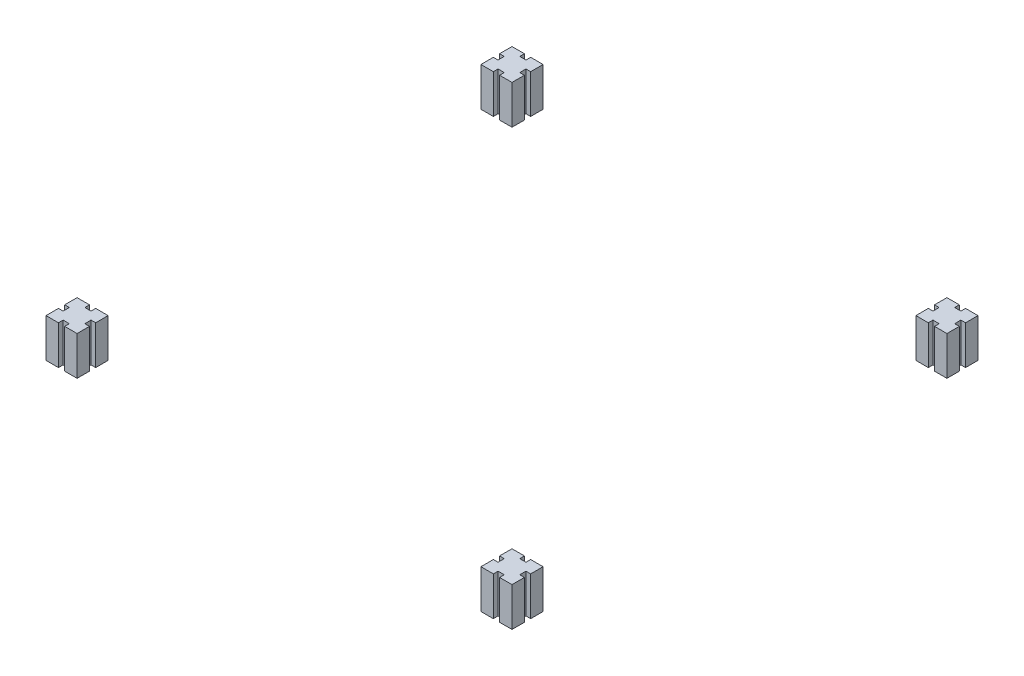
SolidWorks part; units mm, degrees
ref_plane "Front Plane" through (0, 0, 0) normal (0, 0, 1) x (1, 0, 0)
ref_plane "Top Plane" through (0, 0, 0) normal (0, 1, 0) x (1, 0, 0)
ref_plane "Right Plane" through (0, 0, 0) normal (1, 0, 0) x (0, 0, -1)
sketch "Sketch1" plane through (0, 0, 0) normal (0, 1, 0) x (1, 0, 0)
  line L0 (260, 300) -> (-260, 300) construction
  line L1 (-280, -280) -> (280, -280)
  line L2 (-280, -280) -> (-280, 280)
  line L3 (-280, 280) -> (280, 280)
  line L4 (280, -280) -> (280, 280)
  line L5 (-280, -280) -> (280, 280) construction
  line L6 (-280, 280) -> (280, -280) construction
  point P0 (0, 0)
  dimension "D1" = 20
  dimension "D2" = 45
sketch "Sketch2" plane through (0, 0, 0) normal (0, 1, 0) x (1, 0, 0)
  line L0 (0, -44) -> (0, 44) construction
  line L1 (-300, 300) -> (-260, 300)
  line L2 (-300, 300) -> (-300, 260)
  line L3 (-300, 260) -> (-260, 260)
  line L4 (-260, 300) -> (-260, 260)
  line L5 (-300, 300) -> (-260, 260) construction
  line L6 (-300, 260) -> (-260, 300) construction
  line L7 (300, 260) -> (260, 300) construction
  line L8 (300, 300) -> (260, 260) construction
  line L9 (260, 300) -> (260, 260)
  line L10 (300, 260) -> (260, 260)
  line L11 (300, 300) -> (300, 260)
  line L12 (300, 300) -> (260, 300)
  line L13 (-44, 0) -> (44, 0) construction
  line L14 (300, -300) -> (260, -260) construction
  line L15 (300, -260) -> (260, -300) construction
  line L16 (-300, -260) -> (-260, -300) construction
  line L17 (-300, -300) -> (-260, -260) construction
  line L18 (300, -300) -> (260, -300)
  line L19 (300, -300) -> (300, -260)
  line L20 (300, -260) -> (260, -260)
  line L21 (260, -300) -> (260, -260)
  line L22 (-260, -300) -> (-260, -260)
  line L23 (-300, -260) -> (-260, -260)
  line L24 (-300, -300) -> (-300, -260)
  line L25 (-300, -300) -> (-260, -300)
  point P0 (-280, 280)
  point P12 (280, 280)
  point P23 (280, -280)
  point P24 (-280, -280)
  dimension "D1" = 40
  dimension "D2" = 40
extrude "Boss-Extrude1" add sketch "Sketch2" along normal blind 25 and the other way blind 25
sketch "Sketch3" plane through (0, 0, 0) normal (0, 1, 0) x (1, 0, 0)
  line L0 (-280, 300) -> (-280, 260) construction
  line L1 (-260, 300) -> (-300, 300) construction
  line L2 (-300, 260) -> (-260, 260) construction
  line L3 (-300, 280) -> (-260, 280) construction
  line L4 (-300, 300) -> (-300, 260) construction
  line L5 (-260, 260) -> (-260, 300) construction
  line L6 (-254, 284) -> (-254, 276)
  line L7 (-284, 306) -> (-276, 306)
  line L8 (-284, 306) -> (-284, 294)
  line L9 (-284, 294) -> (-276, 294)
  line L10 (-276, 306) -> (-276, 294)
  line L11 (-284, 306) -> (-276, 294) construction
  line L12 (-284, 294) -> (-276, 306) construction
  line L13 (-254, 284) -> (-266, 284)
  line L14 (-266, 284) -> (-266, 276)
  line L15 (-254, 276) -> (-266, 276)
  line L16 (-254, 284) -> (-266, 276) construction
  line L17 (-266, 284) -> (-254, 276) construction
  line L18 (-276, 254) -> (-284, 254)
  line L19 (-276, 254) -> (-276, 266)
  line L20 (-276, 266) -> (-284, 266)
  line L21 (-284, 254) -> (-284, 266)
  line L22 (-276, 254) -> (-284, 266) construction
  line L23 (-276, 266) -> (-284, 254) construction
  line L24 (-306, 276) -> (-306, 284)
  line L25 (-306, 276) -> (-294, 276)
  line L26 (-294, 276) -> (-294, 284)
  line L27 (-306, 284) -> (-294, 284)
  line L28 (-306, 276) -> (-294, 284) construction
  line L29 (-294, 276) -> (-306, 284) construction
  line L30 (0, -55) -> (0, 55) construction
  line L31 (294, 276) -> (306, 284) construction
  line L32 (306, 276) -> (294, 284) construction
  line L33 (276, 266) -> (284, 254) construction
  line L34 (276, 254) -> (284, 266) construction
  line L35 (266, 284) -> (254, 276) construction
  line L36 (254, 284) -> (266, 276) construction
  line L37 (284, 294) -> (276, 306) construction
  line L38 (284, 306) -> (276, 294) construction
  line L39 (300, 280) -> (260, 280) construction
  line L40 (280, 300) -> (280, 260) construction
  line L41 (306, 284) -> (294, 284)
  line L42 (294, 276) -> (294, 284)
  line L43 (306, 276) -> (294, 276)
  line L44 (306, 276) -> (306, 284)
  line L45 (284, 254) -> (284, 266)
  line L46 (276, 266) -> (284, 266)
  line L47 (276, 254) -> (276, 266)
  line L48 (276, 254) -> (284, 254)
  line L49 (254, 276) -> (266, 276)
  line L50 (266, 284) -> (266, 276)
  line L51 (254, 284) -> (266, 284)
  line L52 (276, 306) -> (276, 294)
  line L53 (284, 294) -> (276, 294)
  line L54 (284, 306) -> (284, 294)
  line L55 (284, 306) -> (276, 306)
  line L56 (254, 284) -> (254, 276)
  line L57 (-55, 0) -> (55, 0) construction
  line L58 (280, -300) -> (280, -260) construction
  line L59 (300, -280) -> (260, -280) construction
  line L60 (284, -306) -> (276, -294) construction
  line L61 (284, -294) -> (276, -306) construction
  line L62 (254, -284) -> (266, -276) construction
  line L63 (266, -284) -> (254, -276) construction
  line L64 (276, -254) -> (284, -266) construction
  line L65 (276, -266) -> (284, -254) construction
  line L66 (306, -276) -> (294, -284) construction
  line L67 (294, -276) -> (306, -284) construction
  line L68 (-294, -276) -> (-306, -284) construction
  line L69 (-306, -276) -> (-294, -284) construction
  line L70 (-276, -266) -> (-284, -254) construction
  line L71 (-276, -254) -> (-284, -266) construction
  line L72 (-266, -284) -> (-254, -276) construction
  line L73 (-254, -284) -> (-266, -276) construction
  line L74 (-284, -294) -> (-276, -306) construction
  line L75 (-284, -306) -> (-276, -294) construction
  line L76 (-300, -280) -> (-260, -280) construction
  line L77 (-280, -300) -> (-280, -260) construction
  line L78 (254, -284) -> (254, -276)
  line L79 (284, -306) -> (276, -306)
  line L80 (284, -306) -> (284, -294)
  line L81 (284, -294) -> (276, -294)
  line L82 (276, -306) -> (276, -294)
  line L83 (254, -284) -> (266, -284)
  line L84 (266, -284) -> (266, -276)
  line L85 (254, -276) -> (266, -276)
  line L86 (276, -254) -> (284, -254)
  line L87 (276, -254) -> (276, -266)
  line L88 (276, -266) -> (284, -266)
  line L89 (284, -254) -> (284, -266)
  line L90 (306, -276) -> (306, -284)
  line L91 (306, -276) -> (294, -276)
  line L92 (294, -276) -> (294, -284)
  line L93 (306, -284) -> (294, -284)
  line L94 (-306, -284) -> (-294, -284)
  line L95 (-294, -276) -> (-294, -284)
  line L96 (-306, -276) -> (-294, -276)
  line L97 (-306, -276) -> (-306, -284)
  line L98 (-284, -254) -> (-284, -266)
  line L99 (-276, -266) -> (-284, -266)
  line L100 (-276, -254) -> (-276, -266)
  line L101 (-276, -254) -> (-284, -254)
  line L102 (-254, -276) -> (-266, -276)
  line L103 (-266, -284) -> (-266, -276)
  line L104 (-254, -284) -> (-266, -284)
  line L105 (-276, -306) -> (-276, -294)
  line L106 (-284, -294) -> (-276, -294)
  line L107 (-284, -306) -> (-284, -294)
  line L108 (-284, -306) -> (-276, -306)
  line L109 (-254, -284) -> (-254, -276)
  point P16 (-280, 280)
  point P32 (-280, 280)
  point P54 (280, 280)
  point P97 (280, -280)
  point P98 (-280, -280)
  dimension "D1" = 8
  dimension "D2" = 12
  dimension "D3" = 4
extrude "Cut-Extrude1" cut sketch "Sketch3" against normal through all both and the other way through all
